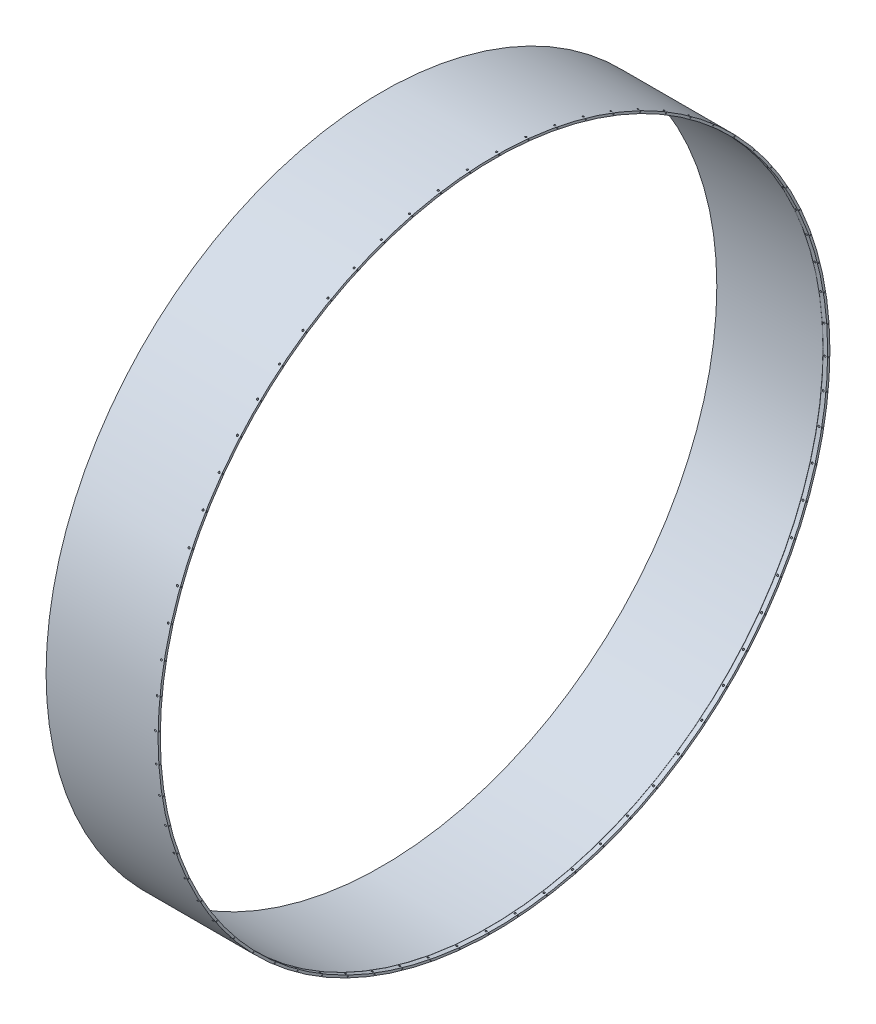
SolidWorks part; units mm, degrees
material "СТЕКЛОПЛАСТИК"
ref_plane "Спереди" through (0, 0, 0) normal (0, 0, 1) x (1, 0, 0)
ref_plane "Сверху" through (0, 0, 0) normal (0, 1, 0) x (1, 0, 0)
ref_plane "Справа" through (0, 0, 0) normal (1, 0, 0) x (0, 0, -1)
sketch "Эскиз1" plane through (0, 0, 0) normal (0, 0, 1) x (1, 0, 0)
  line L0 (0, 0) -> (578.3133, 0) construction
  line L1 (0, -1500) -> (500, -1500)
  line L6 (500, -1500) -> (500, -1490)
  line L7 (500, -1490) -> (480, -1490)
  line L9 (475, -1495) -> (0, -1495)
  line L10 (0, -1495) -> (0, -1500)
  arc A0 (480, -1490) -> (477.5, -1492.5) centre (480, -1492.5) ccw
  arc A1 (475, -1495) -> (477.5, -1492.5) centre (475, -1492.5) ccw
  dimension "D5" = 10
  dimension "D3" = 2.5
  dimension "D4" = 2.5
  dimension "D1" = 3000
  dimension "D2" = 500
  dimension "D6" = 5
  dimension "D7" = 20
revolve "Повернуть1" add sketch "Эскиз1" angle 360 about L0
hole_wizard "Отверстие1" positions "Трехмерный эскиз2" profile "Эскиз3" legacy
sketch3d "Трехмерный эскиз2"
  point P0 (488, 879.5768, 1215.0492)
  dimension "D1" = 12
sketch "Эскиз3" plane through (488, 879.5768, 1215.0492) normal (1, 0, 0) x (0, -0.81, 0.5864)
  line L0 (0, 0) -> (0, 100)
  line L1 (0, 100) -> (4, 100)
  line L2 (4, 100) -> (4, 0)
  line L3 (4, 0) -> (0, 0)
  line L4 (0, 110) -> (0, -10) construction
  dimension "Диаметр" = 8
  dimension "Глубина" = 100
ref_plane "Плоскость1" through (0, 0, 0) normal (0, 0.81, -0.5864) x (0, 0.5864, 0.81)
hole_wizard "Отверстие2" positions "Эскиз4" profile "Эскиз5" legacy end condition up to next
sketch "Эскиз4" plane through (500, 0, 0) normal (1, 0, 0) x (0, 0, -1)
  line L0 (1866.3874, -1351.082) -> (-1866.3874, 1351.082) construction
  circle A0 centre (0, 0) radius 1500 construction
  point P0 (-1210.9991, 876.6449)
  dimension "D1" = 1495
sketch "Эскиз5" plane through (500, 876.6449, 1210.9991) normal (0, 1, 0) x (0, 0, -1)
  line L0 (0, 0) -> (0, 8)
  line L1 (0, 8) -> (2.5, 8)
  line L2 (2.5, 8) -> (2.5, 0)
  line L3 (2.5, 0) -> (0, 0)
  line L4 (0, 110) -> (0, -10) construction
  dimension "Диаметр" = 5
  dimension "Глубина" = 8
pattern_circular "Круговой массив1" count 72 over 360 about axis through (0, 0, 0) along (1, 0, 0) of "Отверстие2", "Отверстие1" reverse direction yes
